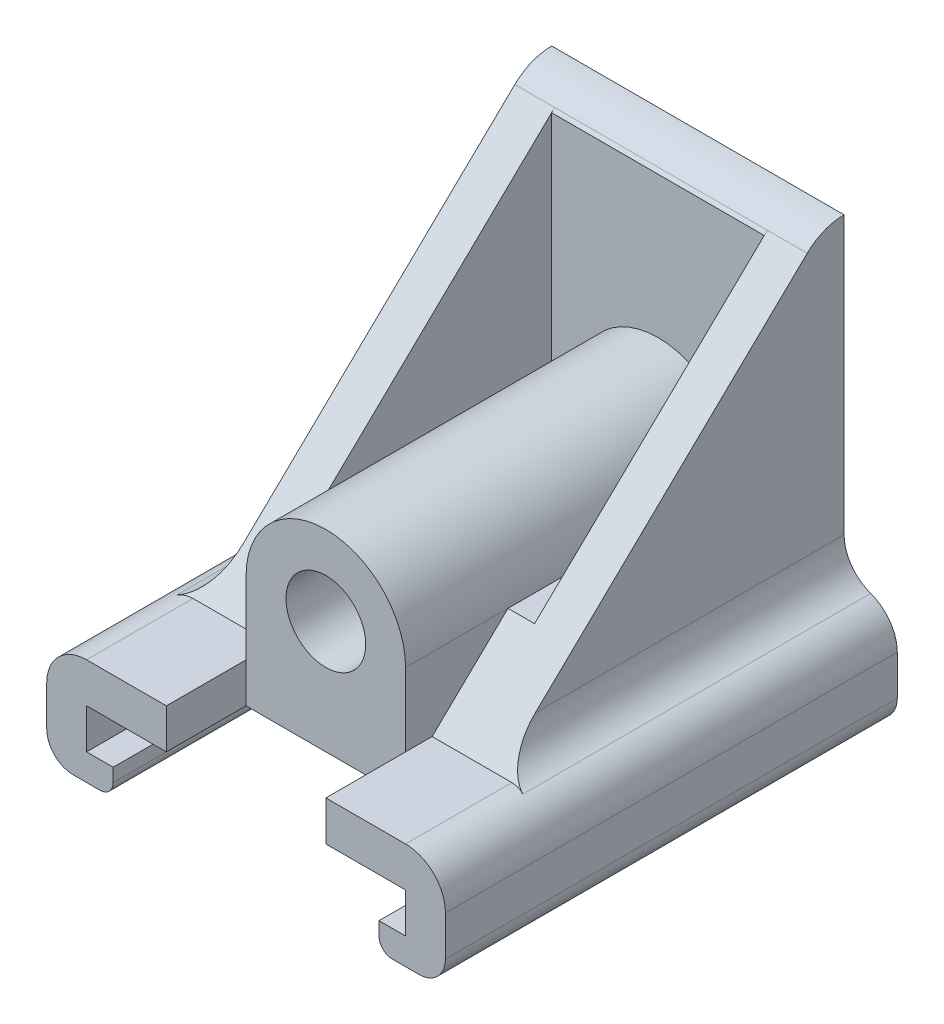
SolidWorks part; units mm, degrees
ref_plane "Front Plane" through (0, 0, 0) normal (0, 0, 1) x (1, 0, 0)
ref_plane "Top Plane" through (0, 0, 0) normal (0, 1, 0) x (1, 0, 0)
ref_plane "Right Plane" through (0, 0, 0) normal (1, 0, 0) x (0, 0, -1)
sketch "Sketch1" plane through (0, 0, 0) normal (0, 0, 1) x (1, 0, 0)
  line L0 (0, 0) -> (0, -25.4) construction
  line L1 (19.05, 0) -> (38.1, 0)
  line L2 (47.625, -9.525) -> (47.625, -19.05)
  line L3 (41.275, -25.4) -> (34.925, -25.4)
  line L4 (31.75, -22.225) -> (31.75, -19.05)
  line L5 (31.75, -19.05) -> (38.1, -19.05)
  line L6 (38.1, -19.05) -> (38.1, -9.525)
  line L7 (38.1, -9.525) -> (19.05, -9.525)
  line L8 (19.05, -9.525) -> (19.05, 0)
  line L9 (19.05, -9.525) -> (19.05, 17.4625)
  line L10 (0, 0) -> (0, 36.5125) construction
  line L11 (19.05, -9.525) -> (-19.05, -9.525)
  line L12 (-19.05, -9.525) -> (-19.05, 17.4625)
  line L13 (-19.05, -9.525) -> (-19.05, 0)
  line L14 (-38.1, -9.525) -> (-19.05, -9.525)
  line L15 (-38.1, -19.05) -> (-38.1, -9.525)
  line L16 (-31.75, -19.05) -> (-38.1, -19.05)
  line L17 (-31.75, -22.225) -> (-31.75, -19.05)
  line L18 (-41.275, -25.4) -> (-34.925, -25.4)
  line L19 (-47.625, -9.525) -> (-47.625, -19.05)
  line L20 (-19.05, 0) -> (-38.1, 0)
  line L21 (0, 36.5125) -> (34.925, 36.5125) construction
  line L22 (34.925, 0) -> (34.925, 74.6125)
  line L23 (25.4, 74.6125) -> (25.4, 0)
  line L24 (25.4, 74.6125) -> (34.925, 74.6125)
  line L25 (25.4, 17.4625) -> (19.05, 17.4625)
  line L26 (-25.4, 17.4625) -> (-19.05, 17.4625)
  line L27 (-34.925, 0) -> (-34.925, 74.6125)
  line L28 (-25.4, 74.6125) -> (-34.925, 74.6125)
  line L29 (-25.4, 74.6125) -> (-25.4, 0)
  line L30 (-25.4, 74.6125) -> (25.4, 74.6125)
  arc A0 (47.625, -19.05) -> (41.275, -25.4) centre (41.275, -19.05) cw
  arc A1 (47.625, -9.525) -> (38.1, 0) centre (38.1, -9.525) ccw
  arc A2 (34.925, -25.4) -> (31.75, -22.225) centre (34.925, -22.225) cw
  arc A3 (19.05, 17.4625) -> (-19.05, 17.4625) centre (0, 17.4625) ccw
  arc A4 (-34.925, -25.4) -> (-31.75, -22.225) centre (-34.925, -22.225) ccw
  arc A5 (-47.625, -9.525) -> (-38.1, 0) centre (-38.1, -9.525) cw
  arc A6 (-47.625, -19.05) -> (-41.275, -25.4) centre (-41.275, -19.05) ccw
  point P17 (31.75, -25.4)
  point P34 (0, -9.525)
  point P37 (-31.75, -25.4)
  dimension "D6" = 6.35
  dimension "D7" = 9.525
  dimension "D8" = 3.175
  dimension "D11" = 38.1
  dimension "D1" = 25.4
  dimension "D2" = 9.525
  dimension "D3" = 9.525
  dimension "D4" = 6.35
  dimension "D5" = 6.35
  dimension "D9" = 47.625
  dimension "D10" = 19.05
  dimension "D12" = 26.9875
  dimension "D13" = 34.925
  dimension "D14" = 9.525
  dimension "D15" = 74.6125
extrude "Boss-Extrude1" add sketch "Sketch1" along normal blind 107.95 contours A2 L3 A0 L2 A1 L1 L8 L7 L6 L5 L4 | L19 A6 L18 A4 L17 L16 L15 L14 L12 L20 A5 region at (22.225, -0.3823, 0) region at (-28.575, -9.1427, 0)
extrude "Boss-Extrude2" add sketch "Sketch1<6>" along normal blind 82.55 contours L23 L25 L9 L1 | L24 L23 L1 L22 region at (22.225, 8.7312, 0) region at (30.1625, 37.3062, 0)
sketch "Sketch1<6>" plane through (0, 0, 0) normal (0, 0, 1) x (1, 0, 0) same geometry as "Sketch1"
sketch "Sketch3" plane through (34.925, 0, 0) normal (1, 0, 0) x (0, 0, -1)
  line L0 (-82.55, 0) -> (-8.8125, 71.0574)
  line L1 (0, 0) -> (0, 74.6125) construction
  line L2 (-82.55, 0) -> (-82.55, 74.6125)
  line L3 (-82.55, 74.6125) -> (0, 74.6125)
  arc A0 (0, 74.6125) -> (-8.8125, 71.0574) centre (0, 61.9125) ccw
  dimension "D1" = 25.4
extrude "Cut-Extrude2" cut sketch "Sketch3" against normal up to surface (15.875 mm away) up to face at (19.05, 2.6458, 63.5)
extrude "Boss-Extrude4" add sketch "Sketch1<8>" along normal blind 88.9 contours L9 A3 L12 L11 L8 region at (0, 11.6651, 0)
sketch "Sketch1<8>" plane through (0, 0, 0) normal (0, 0, 1) x (1, 0, 0) same geometry as "Sketch1"
mirror "Mirror1" about plane through (0, 0, 0) normal (1, 0, 0) of "Boss-Extrude2", "Cut-Extrude2"
sketch "Sketch4" plane through (-25.4, 0, 0) normal (1, 0, 0) x (0, 0, -1)
  line L0 (0, 74.6125) -> (0, 17.4625)
  line L1 (0, 17.4625) -> (-9.525, 17.4625)
  line L2 (-64.4289, 17.4625) -> (0, 17.4625) construction
  line L3 (-9.525, 17.4625) -> (-9.525, 70.3128)
  line L4 (-9.525, 70.3128) -> (-8.8125, 71.0574)
  line L7 (-8.8125, 71.0574) -> (-64.4289, 17.4625)
  line L8 (-64.4289, 17.4625) -> (0, 17.4625)
  line L9 (0, 17.4625) -> (0, 74.6125)
  line L11 (-64.4289, 17.4625) -> (0, 17.4625)
  line L12 (0, 17.4625) -> (0, 74.6125)
  arc A0 (0, 74.6125) -> (-8.8125, 71.0574) centre (0, 61.9125) ccw construction
  arc A2 (0, 74.6125) -> (-8.8125, 71.0574) centre (0, 61.9125) ccw
  arc A3 (0, 74.6125) -> (-9.525, 70.3128) centre (0, 61.9125) ccw
  arc M2 (0, 74.6125) -> (-8.8125, 71.0574) centre (0, 61.9125) ccw
  line M4 (-64.4289, 17.4625) -> (0, 17.4625)
  line M5 (0, 17.4625) -> (0, 74.6125)
  dimension "D2" = 0
  dimension "D1" = 9.525
extrude "Boss-Extrude6" add sketch "Sketch4" along normal up to surface (50.8 mm away) contours L4 L3 M4 M5 M2 region at (-25.4, 45.3911, 4.7041) up to face at (25.4, 45.3625, 18.3966)
sketch "Sketch5" plane through (0, 0, 88.9) normal (0, 0, 1) x (1, 0, 0)
  circle A0 centre (0, 17.4625) radius 9.525
  dimension "D1" = 19.05
extrude "Cut-Extrude3" cut sketch "Sketch5" against normal blind 31.75
fillet "Fillet2" radius 9.525 2 edges at (-34.925, 0, 41.275) (34.925, 0, 41.275)
